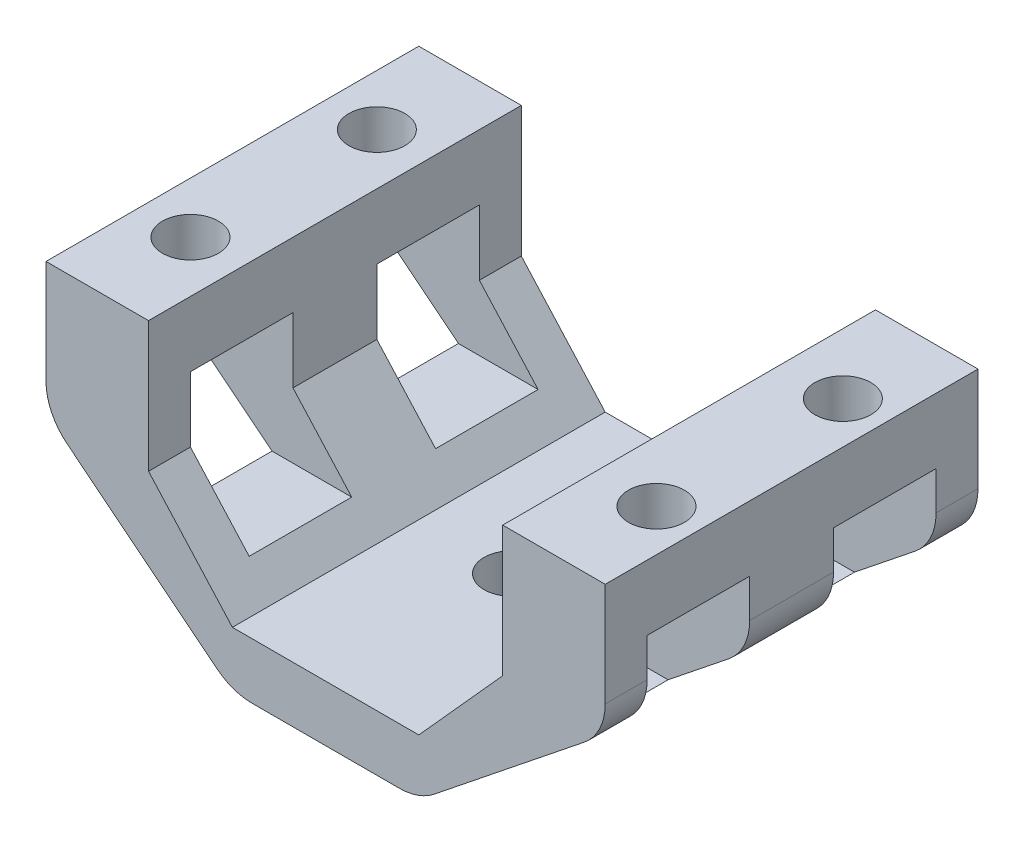
SolidWorks part; units mm, degrees
ref_plane "Alzado" through (0, 0, 0) normal (0, 0, 1) x (1, 0, 0)
ref_plane "Planta" through (0, 0, 0) normal (0, 1, 0) x (1, 0, 0)
ref_plane "Vista lateral" through (0, 0, 0) normal (1, 0, 0) x (0, 0, -1)
sketch "Croquis1" plane through (0, 0, 0) normal (0, 0, 1) x (1, 0, 0)
  line L0 (0, 0) -> (0, -5) construction
  line L21 (0, 0) -> (-4.5, 0) construction
  line L22 (-10, 0) -> (0, -8)
  line L23 (-4.5, 0) -> (-10, 0)
  line L24 (-4.5, 0) -> (-4.5, 7)
  line L25 (-4.5, 7) -> (-10, 7)
  line L26 (-10, 0) -> (-10, 7)
  line L27 (0, -5) -> (10, -5)
  line L28 (0, -5) -> (0, -8)
  line L29 (0, -8) -> (10, -8)
  line L30 (5, -5) -> (5, -8)
  line L31 (0, -5) -> (-4.5, 0)
  line L32 (10, -5) -> (10, -8)
  line L33 (20, 0) -> (10, -8)
  line L34 (10, -5) -> (14.5, 0)
  line L35 (14.5, 7) -> (20, 7)
  line L36 (20, 0) -> (20, 7)
  line L37 (14.5, 0) -> (20, 0)
  line L38 (14.5, 0) -> (14.5, 7)
  dimension "D1" = 7
  dimension "D2" = 4.5
  dimension "D3" = 5
  dimension "D4" = 3
  dimension "D5" = 5
  dimension "D6" = 5.5
extrude "Saliente-Extruir1" add sketch "Croquis1" along normal blind 20 contours L26 L23 L24 L25 | L28 L31 L23 L22 | L30 L27 L28 L29 | L32 L27 L30 L29 | L37 L34 L32 L33 | L38 L37 L36 L35 region at (-4.0507, -3.058, 0) region at (-7.25, 3.5, 0) region at (2.5, -6.5, 0) region at (7.5, -6.5, 0) region at (14.0507, -3.058, 0) region at (17.25, 3.5, 0)
sketch "Croquis2" plane through (-10, 0, 0) normal (-1, 0, 0) x (0, 0, 1)
  line L0 (10, 7) -> (10, 0) construction
  line L1 (0, 0) -> (0, -8) construction
  line L2 (20, 7) -> (0, 7) construction
  line L3 (20, 0) -> (0, 0) construction
  line L8 (0, 7) -> (10, 7) construction
  line L9 (5, 7) -> (5, 0) construction
  line L15 (17.75, 3.5) -> (12.25, 3.5)
  line L16 (2.25, -3.5) -> (7.75, -3.5)
  line L17 (2.25, -3.5) -> (2.25, 3.5)
  line L18 (2.25, 3.5) -> (7.75, 3.5)
  line L19 (7.75, -3.5) -> (7.75, 3.5)
  line L20 (2.25, -3.5) -> (7.75, 3.5) construction
  line L21 (2.25, 3.5) -> (7.75, -3.5) construction
  line L22 (12.25, -3.5) -> (12.25, 3.5)
  line L23 (17.75, -3.5) -> (12.25, -3.5)
  line L24 (17.75, -3.5) -> (17.75, 3.5)
  dimension "D1" = 5.5
  dimension "D2" = 3.5
extrude "Cortar-Extruir3" cut sketch "Croquis2" against normal through all
sketch "Croquis3" plane through (0, 7, 0) normal (0, 1, 0) x (1, 0, 0)
  line L0 (-7.25, 0) -> (-7.25, -5) construction
  line L1 (-4.5, 0) -> (-10, 0) construction
  circle A0 centre (-7.25, -5) radius 1.5
  circle A1 centre (17.75, -5) radius 1.5
  circle A2 centre (17.75, -15) radius 1.5
  circle A3 centre (-7.25, -15) radius 1.5
  dimension "D1" = 3
  dimension "D2" = 2
  dimension "D3" = 2
extrude "Cortar-Extruir4" cut sketch "Croquis3" against normal through all
fillet "Redondeo1" radius 3 8 edges at (10, -8, 10) (20, 0, 1.125) (20, 0, 18.875) (20, 0, 10) (0, -8, 10) (-10, 0, 18.875) (-10, 0, 1.125) (-10, 0, 10)
sketch "Croquis4" plane through (0, -5, 0) normal (0, 1, 0) x (1, 0, 0)
  line L0 (5, 0) -> (5, -20) construction
  line L1 (0, 0) -> (10, 0) construction
  line L2 (0, -20) -> (10, -20) construction
  circle A0 centre (5, -10) radius 1.5
extrude "Cortar-Extruir5" cut sketch "Croquis4" against normal through all
